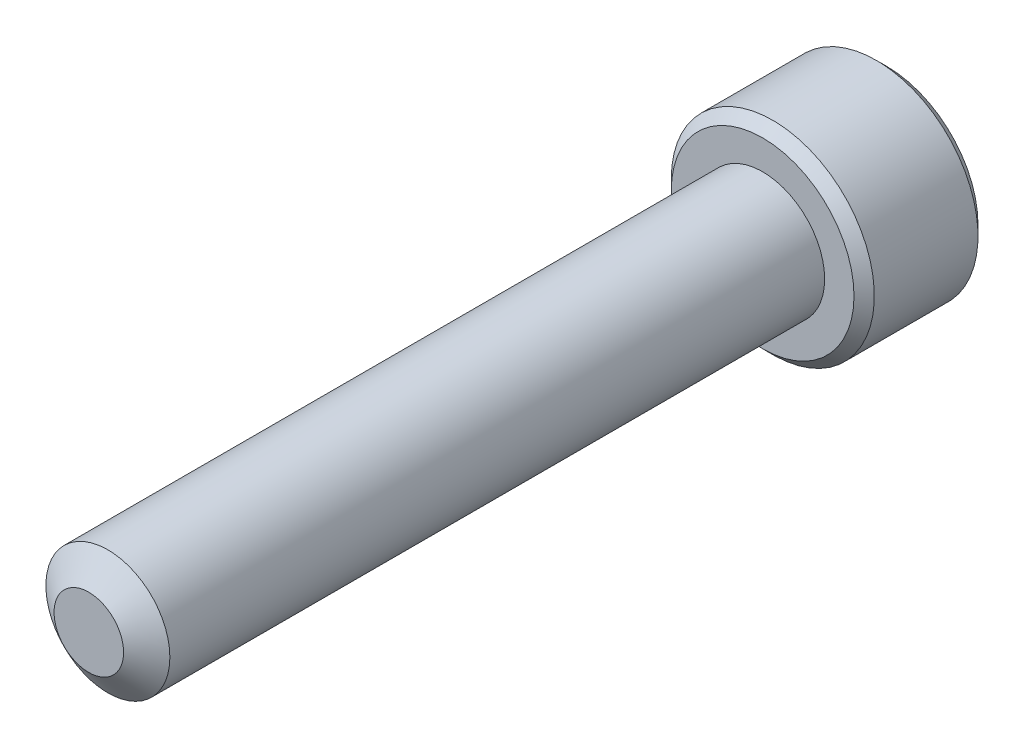
SolidWorks part; units mm, degrees
material "Alloy Steel"
ref_plane "Front Plane" through (0, 0, 0) normal (0, 0, 1) x (1, 0, 0)
ref_plane "Top Plane" through (0, 0, 0) normal (0, 1, 0) x (1, 0, 0)
ref_plane "Right Plane" through (0, 0, 0) normal (1, 0, 0) x (0, 0, -1)
sketch "Sketch1" plane through (0, 0, 0) normal (0, 0, 1) x (1, 0, 0)
  circle A0 centre (0, 0) radius 1.7526
  dimension "OD" = 3.5052
extrude "Extrude1" add sketch "Sketch1" against normal blind 19.05
sketch "Sketch2" plane through (0, 0, 0) normal (0, 0, 1) x (1, 0, 0)
  circle A0 centre (0, 0) radius 1.7526 construction
  circle A1 centre (0, 0) radius 1.7526
curve "Helix/Spiral1" pitch 0.7937 height 19.8438 turns 25 parameters "pitch"=0.7937
sketch "Sketch3" plane through (0, 0, 0) normal (1, 0, 0) x (0, 0, -1)
  line L0 (-0.6945, 1.7526) -> (-0.3969, 1.237)
  line L1 (-0.3969, 1.237) -> (-0.2977, 1.237)
  line L2 (-0.2977, 1.237) -> (0, 1.7526)
  line L3 (-0.6945, 1.7526) -> (0, 1.7526)
  line L4 (-0.3473, 1.7526) -> (-0.3473, 1.237) construction
  line L5 (-0.5457, 1.4948) -> (-0.1488, 1.4948) construction
  line L6 (0, 1.7526) -> (0, -1.7526) construction
  dimension "D1" = 0.0992
  dimension "D2" = 0.3969
  dimension "D3" = 60
sweep "Cut-Sweep1" [suppressed] cut profiles "Sketch3" path "Helix/Spiral1"
sketch "Sketch4" plane through (0, 0, 0) normal (1, 0, 0) x (0, 0, -1)
  line L0 (0.5388, 1.7526) -> (0, 0.983)
  line L1 (0, 0.983) -> (0, 1.7526)
  line L2 (0.5388, 1.7526) -> (0, 1.7526)
  line L3 (-0.6945, 1.7526) -> (0, 1.7526) construction
  line L4 (0, 0) -> (7.0209, 0) construction
  dimension "D1" = 55
  dimension "D2" = 0.254
revolve "Cut-Revolve1" cut sketch "Sketch4" angle 360 about L4
sketch "Sketch5" [suppressed] plane through (0, 0, 0) normal (1, 0, 0) x (0, 0, -1)
  line L0 (19.05, -1.2539) -> (19.05, 1.2505) construction
  line L1 (19.05, 1.8796) -> (87.4327, 1.8796)
  line L2 (19.05, 1.8796) -> (19.05, 0)
  line L3 (19.05, 0) -> (87.3125, 0)
  line L4 (87.3125, 1.5494) -> (87.3125, 0)
  line L5 (87.4327, 1.8796) -> (87.3125, 1.5494)
  line L6 (0, 0) -> (9.9695, 0) construction
  point P3 (87.3125, 1.8796)
  point P10 (87.3125, 1.8796)
  dimension "D1" = 0.3302
  dimension "Thread min" = 87.3125
  dimension "D2" = 0.127
  dimension "D3" = 20
revolve "partially thread" [suppressed] add sketch "Sketch5" angle 360 about L6
sketch "Sketch6" plane through (0, 0, -19.05) normal (0, 0, -1) x (-1, 0, 0)
  circle A0 centre (0, 0) radius 2.8702
  dimension "head dia" = 5.7404
extrude "Extrude2" add sketch "Sketch6" along normal blind 3.5052
sketch "Sketch7" plane through (0, 0, -22.5552) normal (0, 0, -1) x (-1, 0, 0)
  line L1 (0, 1.604) -> (-1.3891, 0.802)
  line L2 (-1.3891, 0.802) -> (-1.3891, -0.802)
  line L3 (-1.3891, -0.802) -> (0, -1.604)
  line L4 (0, -1.604) -> (1.3891, -0.802)
  line L5 (1.3891, -0.802) -> (1.3891, 0.802)
  line L6 (1.3891, 0.802) -> (0, 1.604)
  circle A0 centre (0, 0) radius 1.3891 construction
  dimension "hex dia" = 2.7781
extrude "Cut-Extrude1" cut sketch "Sketch7" against normal blind 2.0836
sketch "Sketch8" plane through (0, 0, -22.5552) normal (0, 0, -1) x (-1, 0, 0)
  circle A0 centre (0, 0) radius 1.604
extrude "Cut-Extrude2" cut sketch "Sketch8" against normal through all draft 45
chamfer "Chamfer1" distance 0.287 angle 45 2 edges at (-2.8702, 0, -22.5552) (-2.8702, 0, -19.05)
sketch "Sketch9" plane through (0, 0, 0) normal (1, 0, 0) x (0, 0, -1)
  line L0 (0, 1.7526) -> (0, -1.7526) construction
  line L1 (4.3656, 1.7526) -> (4.3656, -1.7526) construction
  dimension "D1" = 4.3656
equation "\"D3@Helix/Spiral1\" = \"screw length@Extrude1\"+\"pitch@Helix/Spiral1\""
equation "\"D1@Sketch3\" = \"pitch@Helix/Spiral1\"*.125"
equation "\"D2@Sketch3\" = \"pitch@Helix/Spiral1\"*.5"
equation "\"D1@Cut-Extrude1\" = \"hex dia@Sketch7\"*.75"
equation "\"D1@Chamfer1\" = \"head dia@Sketch6\"*.05"
equation "\"D1@Sketch9\" = \"pitch@Helix/Spiral1\"*5.5"
